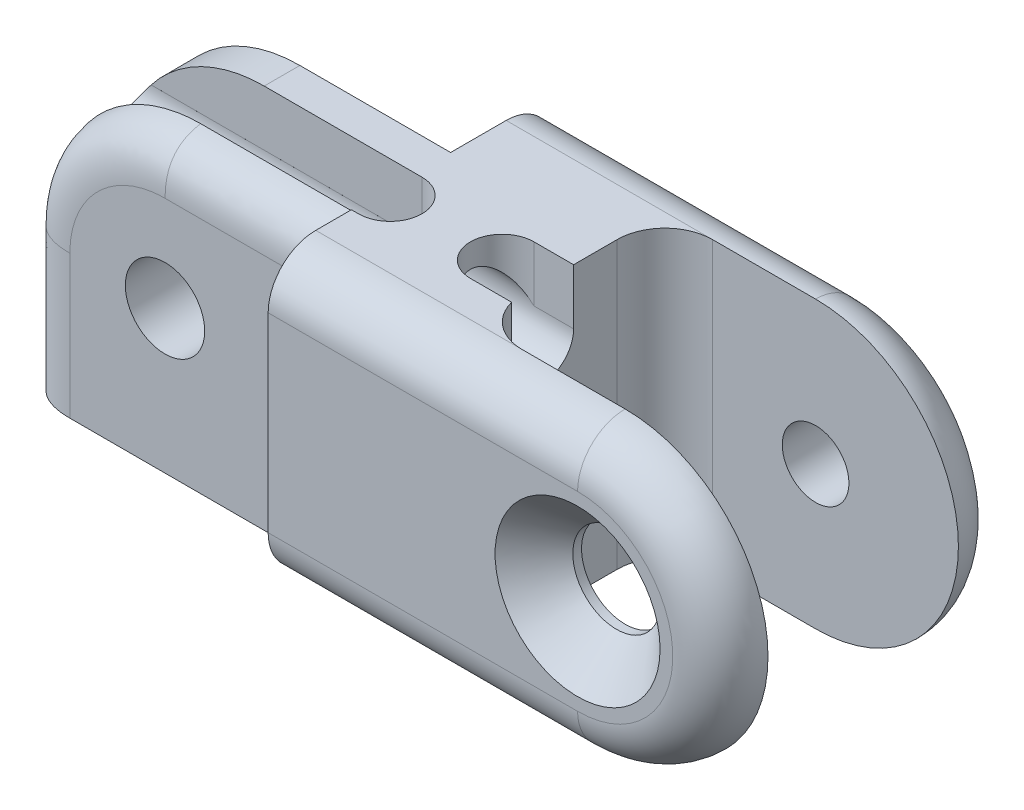
SolidWorks part; units mm, degrees
ref_plane "Front Plane" through (0, 0, 0) normal (0, 0, 1) x (1, 0, 0)
ref_plane "Top Plane" through (0, 0, 0) normal (0, 1, 0) x (1, 0, 0)
ref_plane "Right Plane" through (0, 0, 0) normal (1, 0, 0) x (0, 0, -1)
sketch "Sketch2" plane through (0, 0, 0) normal (0, 1, 0) x (1, 0, 0)
  line L0 (-5, 9) -> (23.5, 9)
  line L1 (23.5, 9) -> (23.5, 6)
  line L2 (23.5, 6) -> (8, 6)
  line L3 (5, 3) -> (5, -3)
  line L4 (8, -6) -> (23.5, -6)
  line L5 (23.5, -6) -> (23.5, -9)
  line L7 (-23.5, -6) -> (-23.5, 2.5)
  line L8 (-49.3622, 0) -> (56.3776, 0) construction
  line L9 (0, 21.2372) -> (0, -19.0689) construction
  line L10 (5, 3) -> (8, 3) construction
  line L11 (8, 3) -> (8, 6) construction
  line L16 (-5, -9) -> (23.5, -9)
  line L18 (-23.5, -6) -> (-5, -6)
  line L19 (-5, -6) -> (-5, -9)
  line L20 (-23.5, 2.5) -> (-5, 2.5)
  line L21 (-5, 2.5) -> (-5, 9)
  arc A0 (8, 6) -> (5, 3) centre (8, 3) ccw
  arc A1 (8, -6) -> (5, -3) centre (8, -3) cw
  point P13 (8, 3)
  dimension "D1" = 47
  dimension "D2" = 18
  dimension "D3" = 3
  dimension "D4" = 18.5
  dimension "D5" = 12
  dimension "D6" = 3
  dimension "D7" = 3
  dimension "D8" = 6.5
  dimension "D9" = 3
  dimension "D10" = 8.5
  dimension "D11" = 18.5
extrude "Boss-Extrude1" add sketch "Sketch2" along normal blind 18
sketch "Sketch5" plane through (0, 0, 9) normal (0, 0, 1) x (1, 0, 0)
  line L0 (-23.5, 9) -> (31.8491, 9) construction
  line L1 (-14.5, 18) -> (-14.5, 0) construction
  line L2 (23.5, 18) -> (23.5, 0) construction
  line L3 (-5, 18) -> (23.5, 18) construction
  line L4 (14.5, 18) -> (14.5, 0) construction
  line L5 (-23.5, 18) -> (-23.5, 0) construction
  line L6 (-23.5, 9) -> (-23.5, 0)
  line L7 (-23.5, 18) -> (-5, 18) construction
  line L8 (-23.5, 0) -> (14.5, 0)
  line L9 (-14.5, 18) -> (14.5, 18)
  arc A0 (-14.5, 18) -> (-23.5, 9) centre (-14.5, 9) ccw
  arc A1 (14.5, 0) -> (14.5, 18) centre (14.5, 9) ccw
  circle A2 centre (-14.5, 9) radius 2.5
  dimension "D2" = 5
  dimension "D1" = 9
extrude "Cut-Extrude1" cut sketch "Sketch5" against normal blind 20 flip side to cut
sketch "Sketch6" plane through (0, 0, 9) normal (0, 0, 1) x (1, 0, 0)
  line L0 (14.5, 0) -> (14.5, 18) construction
  point P4 (14.5, 9)
hole_wizard "CSK for M5 Countersunk Flat Head Screw1" positions "Sketch7" profile "Sketch8" countersink size "M5" standard "DIN" end condition up to next
sketch "Sketch7" plane through (0, 0, 9) normal (0, 0, 1) x (1, 0, 0)
  point P0 (14.5, 9)
sketch "Sketch8" plane through (14.5, 9, 9) normal (1, 0, 0) x (0, -1, 0)
  line L0 (0, 0) -> (0, 3)
  line L1 (0, 3) -> (2.75, 3)
  line L2 (2.75, 3) -> (2.75, 2.45)
  line L3 (2.75, 2.45) -> (5.2, 0)
  line L5 (5.2, 0) -> (0, 0)
  line L6 (-2.75, 2.45) -> (-5.2, 0) construction
  line L11 (0, -6.35) -> (0, 107.95) construction
  dimension "Thru Hole Dia." = 5.5
  dimension "Thru Hole Depth" = 3
  dimension "Near C'Sink Dia." = 10.4
  dimension "Near C'Sink Angle" = 90
hole_wizard "M5 Tapped Hole1" positions "Sketch9" profile "Sketch11" tap size "M5" standard "DIN" end condition through all
sketch "Sketch9" plane through (0, 0, 9) normal (0, 0, 1) x (1, 0, 0)
  point P0 (14.5, 9)
sketch "Sketch11" plane through (14.5, 9, 9) normal (1, 0, 0) x (0, -1, 0)
  line L0 (0, 0) -> (0, 18)
  line L1 (0, 18) -> (2.1, 18)
  line L2 (2.1, 18) -> (2.1, 3.1)
  line L3 (2.1, 3.1) -> (5.2, 0)
  line L5 (5.2, 0) -> (0, 0)
  line L6 (-2.1, 3.1) -> (-5.2, 0) construction
  line L11 (0, -6.35) -> (0, 107.95) construction
  dimension "Thru Tap Drill Dia." = 4.2
  dimension "Thru Tap Drill Depth" = 18
  dimension "Near C'Sink Dia." = 10.4
  dimension "Near C'Sink Angle" = 90
cosmetic thread "Hole Thread1" parameters "D2"=5
fillet "Fillet3" radius 3 3 edges at (-23.5, 4.5, 6) (-9.75, 18, 6) (-20.864, 15.364, 6) conic rho 0.5
sketch "Sketch13" plane through (5, 0, 0) normal (1, 0, 0) x (0, 0, -1)
  line L0 (-1.75, 21.4915) -> (-1.75, -4.5302) construction
  line L1 (-3, 18) -> (3, 18) construction
  circle A0 centre (-1.75, 14.5) radius 2
  dimension "D2" = 4
  dimension "D3" = 3.5
  dimension "D1" = 1.75
extrude "Cut-Extrude2" cut sketch "Sketch13" against normal through all both and the other way through all
sketch "Sketch14" plane through (0, 18, 0) normal (0, 1, 0) x (1, 0, 0)
  line L0 (-21.6236, 0.2504) -> (-4.5557, 0.2504)
  line L1 (-21.5557, -3.75) -> (-4.5557, -3.75)
  line L3 (-21.5557, -3.75) -> (-21.6236, 0.2504)
  arc A0 (-4.5557, -3.75) -> (-4.5557, 0.2504) centre (-4.5557, -1.7498) ccw
  spline S1 degree 3 poles (-20.0797, -3) (-19.9473, -2.8693) (-19.8242, -2.7233) (-19.6669, -2.4679) (-19.62, -2.3776) (-19.5431, -2.1872) (-19.5127, -2.0851) (-19.4764, -1.8774) (-19.4703, -1.7698) (-19.4841, -1.5572) (-19.5036, -1.4537) (-19.5944, -1.1509) (-19.6934, -0.9724) (-19.9222, -0.6565) (-20.0506, -0.5207) (-20.3219, -0.2789) (-20.4619, -0.1762) (-20.8834, 0.0849) (-21.1717, 0.1991) (-21.5706, 0.2557) (-21.7006, 0.2556) (-21.9459, 0.209) (-22.0594, 0.1634) (-22.269, 0.0188) (-22.3624, -0.0793) (-22.5226, -0.3256) (-22.5911, -0.4779) (-22.6703, -0.7331) (-22.6932, -0.8231) (-22.7322, -1.0133) (-22.7481, -1.1133) (-22.7724, -1.3157) (-22.781, -1.419) (-22.7912, -1.6301) (-22.7926, -1.7379) (-22.7863, -2.055) (-22.7677, -2.2665) (-22.7021, -2.6575) (-22.6546, -2.8399) (-22.5922, -3) knots 0 0 0 0 0.0625 0.0625 0.09375 0.09375 0.125 0.125 0.15625 0.15625 0.1875 0.1875 0.25 0.25 0.3125 0.3125 0.375 0.375 0.5 0.5 0.5625 0.5625 0.625 0.625 0.6875 0.6875 0.75 0.75 0.78125 0.78125 0.8125 0.8125 0.84375 0.84375 0.875 0.875 0.9375 0.9375 1 1 1 1 construction
  spline S2 degree 3 poles (-22.5922, -3) (-22.5381, -3.1387) (-22.4701, -3.2552) (-22.3108, -3.4526) (-22.2195, -3.5323) (-22.0254, -3.6532) (-21.9205, -3.6957) (-21.705, -3.7461) (-21.594, -3.7546) (-21.2507, -3.7337) (-21.0173, -3.6588) (-20.5422, -3.4019) (-20.3092, -3.2263) (-20.0797, -3) knots 0 0 0 0 0.125 0.125 0.25 0.25 0.375 0.375 0.5 0.5 0.75 0.75 1 1 1 1 construction
  dimension "D2" = 2.0002
  dimension "D1" = 17
extrude "Cut-Extrude3" cut sketch "Sketch14" against normal blind 3.5
sketch "Sketch15" plane through (0, 18, 0) normal (0, 1, 0) x (1, 0, 0)
sketch "Sketch16" plane through (0, 18, 0) normal (0, 1, 0) x (1, 0, 0)
  line L0 (-8.0769, -1.75) -> (29.6251, -1.75) construction
  line L1 (2.5, 0.25) -> (19.0559, 0.25)
  line L3 (2.5, -3.75) -> (19.0559, -3.75)
  line L4 (19.0559, 0.25) -> (19.0559, -3.75)
  line L5 (5, -3) -> (5, 3) construction
  arc A0 (2.5, 0.25) -> (2.5, -3.75) centre (2.5, -1.75) ccw
  dimension "D2" = 4
  dimension "D1" = 1.75
  dimension "D3" = 2.5
extrude "Cut-Extrude4" cut sketch "Sketch16" against normal blind 3.5
fillet "Fillet4" radius 3 6 edges at (4.75, 0, 9) (23.5, 9, 9) (4.75, 18, 9) (4.75, 0, -9) (23.5, 9, -9) (4.75, 18, -9)
